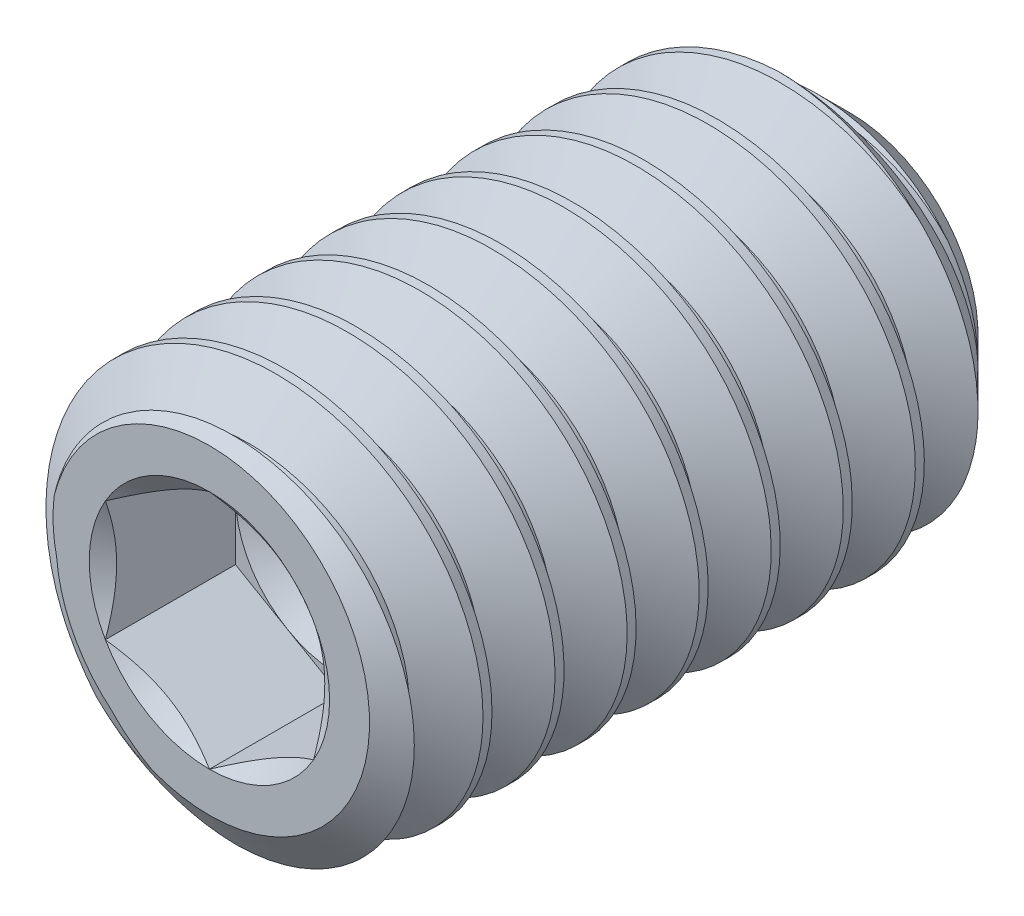
SolidWorks part; units mm, degrees
ref_plane "Front" through (0, 0, 0) normal (0, 0, 1) x (1, 0, 0)
ref_plane "Top" through (0, 0, 0) normal (0, 1, 0) x (1, 0, 0)
ref_plane "Right" through (0, 0, 0) normal (1, 0, 0) x (0, 0, -1)
sketch "Sketch22" plane through (0, 0, 0) normal (1, 0, 0) x (0, 0, -1)
  line L0 (-2, 0) -> (-2, 1)
  line L1 (-2, 1) -> (-1.8249, 1.25)
  line L2 (-1.8249, 1.25) -> (1.55, 1.25)
  line L3 (1.55, 1.25) -> (2, 0.8)
  line L4 (-0.1375, 1.25) -> (-0.1375, -1.25) construction
  line L5 (2, 0) -> (-2, 0)
  line L6 (-2, 1) -> (-2, -1) construction
  line L7 (2, 0) -> (2, 0.8)
  point P11 (-0.1375, 0)
  dimension "Length" = 4
  dimension "D3" = 35
  dimension "D6" = 45
  dimension "Dia" = 2.5
  dimension "D1" = 2
  dimension "D2" = 0.45
revolve "Revolve1" add sketch "Sketch22" angle 360 about L5
ref_plane "Plane1" through (0, 0, -2) normal (0, 0, 1) x (1, 0, 0)
sketch "Sketch27" plane through (0, 0, -2) normal (0, 0, 1) x (1, 0, 0)
  circle A0 centre (0, 0) radius 1.25 construction
  circle A1 centre (0, 0) radius 1.25
curve "Helix/Spiral1" pitch 0.45 height 4.45 radius 1.25 centre (0, 0, -2) axis (0, 0, 1) start towards (0, 1, 0)
sketch "Sketch28" plane through (0, 0, 0) normal (1, 0, 0) x (0, 0, -1)
  line L0 (2, 1.25) -> (2.3938, 1.25)
  line L1 (2.3938, 1.25) -> (2.225, 0.9577)
  line L2 (2.225, 0.9577) -> (2.1688, 0.9577)
  line L3 (2.1688, 0.9577) -> (2, 1.25)
  line L4 (2.0844, 1.1039) -> (2.3094, 1.1039) construction
  line L6 (-1.8249, 1.25) -> (1.55, 1.25) construction
  dimension "D1" = 0.0563
  dimension "D3" = 60
  dimension "D2" = 0.225
sweep "Cut-Sweep2" cut profiles "Sketch28" path "Helix/Spiral1"
sketch "Sketch23" plane through (0, 0, 2) normal (0, 0, 1) x (1, 0, 0)
  line L1 (0, 0.7506) -> (-0.65, 0.3753)
  line L2 (-0.65, 0.3753) -> (-0.65, -0.3753)
  line L3 (-0.65, -0.3753) -> (0, -0.7506)
  line L4 (0, -0.7506) -> (0.65, -0.3753)
  line L5 (0.65, -0.3753) -> (0.65, 0.3753)
  line L6 (0.65, 0.3753) -> (0, 0.7506)
  circle A0 centre (0, 0) radius 0.65 construction
  dimension "Hex" = 1.3
extrude "Cut-Extrude10" cut sketch "Sketch23" against normal blind 0.8125
sketch "Sketch24" plane through (0, 0, 2) normal (0, 0, 1) x (1, 0, 0)
  circle A0 centre (0, 0) radius 0.7506
extrude "Cut-Extrude11" cut sketch "Sketch24" against normal through all draft 55
sketch "Sketch26" plane through (0, 0, 1.1875) normal (0, 0, 1) x (1, 0, 0)
  circle A0 centre (0, 0) radius 0.65 construction
  circle A1 centre (0, 0) radius 0.65
extrude "Cut-Extrude12" cut sketch "Sketch26" against normal through all draft 60
sketch "Sketch30" plane through (0, 0, 0) normal (1, 0, 0) x (0, 0, -1)
  line L0 (-1.8249, 1.25) -> (1.55, 1.25) construction
  line L1 (-2, 0) -> (-2, 1) construction
  line L2 (2, 0) -> (2, 0.8) construction
  point P0 (-2, 1.25)
  point P1 (2, 1.25)
  point P2 (2, -1.25)
  point P11 (0.875, -1.25)
  dimension "D1" = 1.125
equation "\"D1@Sketch28\" = \"D4@Helix/Spiral1\" * .125"
equation "\"D2@Sketch28\" = \"D4@Helix/Spiral1\" * .5"
equation "\"D3@Helix/Spiral1\" = \"Length@Sketch22\" + \"D4@Helix/Spiral1\""
equation "\"D1@Sketch30\" = \"D4@Helix/Spiral1\" * 2.5"
equation "\"hex Depth@Cut-Extrude10\" = \"Hex@Sketch23\" * .625"
equation "\"D1@Sketch22\" = \"Dia@Sketch22\" * .8"
equation "\"D2@Sketch22\" = \"D4@Helix/Spiral1\""
